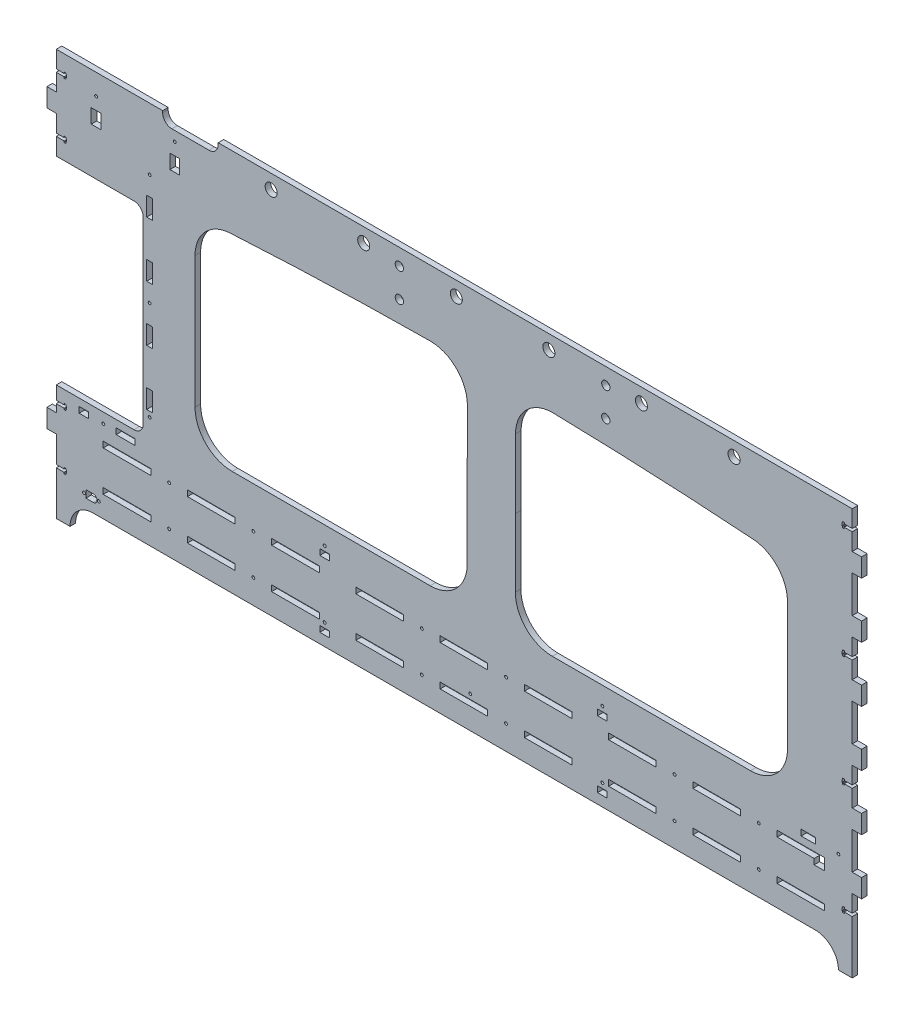
SolidWorks part; units mm, degrees
ref_plane "Płaszczyzna przednia" through (0, 0, 0) normal (0, 0, 1) x (1, 0, 0)
ref_plane "Płaszczyzna górna" through (0, 0, 0) normal (0, 1, 0) x (1, 0, 0)
ref_plane "Płaszczyzna prawa" through (0, 0, 0) normal (1, 0, 0) x (0, 0, -1)
sketch "Szkic1" plane through (0, 0, 0) normal (0, 0, 1) x (1, 0, 0)
  line L0 (0, -69.604) -> (0, -508.604)
  line L1 (0, -69.604) -> (880, -69.604)
  line L2 (0, -508.604) -> (880, -508.604)
  line L3 (880, -69.604) -> (880, -508.604)
  dimension "D1" = 880
  dimension "D2" = 439
extrude "Dodanie-wyciągnięcie1" add sketch "Szkic1" along normal blind 6
sketch "Szkic2" plane through (0, 0, 6) normal (0, 0, 1) x (1, 0, 0)
  line L0 (25, -508.604) -> (855, -508.604)
  line L1 (0, -508.604) -> (880, -508.604) construction
  line L4 (50, -483.604) -> (830, -483.604)
  arc A0 (855, -508.604) -> (830, -483.604) centre (830, -508.604) ccw
  arc A1 (25, -508.604) -> (50, -483.604) centre (50, -508.604) cw
extrude "Wytnij-wyciągnięcie1" cut sketch "Szkic2" against normal blind 6
sketch "Szkic3" plane through (0, 0, 6) normal (0, 0, 1) x (1, 0, 0)
  line L0 (160, -187.6437) -> (160, -329.604)
  line L1 (800, -191.4926) -> (800, -329.604)
  line L2 (200, -369.604) -> (760, -369.604)
  line L3 (0, -69.604) -> (0, -508.604) construction
  line L4 (880, -508.604) -> (880, -69.604) construction
  line L6 (830, -483.604) -> (50, -483.604) construction
  arc A2 (760, -369.604) -> (800, -329.604) centre (760, -329.604) ccw
  arc A3 (762.855, -151.5946) -> (197.6937, -147.7103) centre (450.2341, -4520.4043) ccw
  arc A4 (160, -329.604) -> (200, -369.604) centre (200, -329.604) ccw
  arc A5 (197.6937, -147.7103) -> (160, -187.6437) centre (200, -187.6437) ccw
  arc A6 (762.855, -151.5946) -> (800, -191.4926) centre (760, -191.4926) cw
  dimension "D1" = 40
  dimension "D5" = 40
  dimension "D2" = 160
  dimension "D3" = 114
  dimension "D4" = 80
extrude "Wytnij-wyciągnięcie2" cut sketch "Szkic3" against normal blind 6
sketch "Szkic4" plane through (0, 0, 6) normal (0, 0, 1) x (1, 0, 0)
  line L0 (0, -69.604) -> (0, -508.604) construction
  line L1 (94, -383.604) -> (0, -383.604)
  line L2 (0, -383.604) -> (0, -169.604)
  line L3 (104, -179.604) -> (104, -373.604)
  line L4 (0, -169.604) -> (94, -169.604)
  line L5 (880, -69.604) -> (0, -69.604) construction
  line L6 (830, -483.604) -> (50, -483.604) construction
  arc A0 (94, -383.604) -> (104, -373.604) centre (94, -373.604) ccw
  arc A1 (94, -169.604) -> (104, -179.604) centre (94, -179.604) cw
  dimension "D4" = 10
  dimension "D5" = 104
  dimension "D1" = 100
  dimension "D2" = 100
extrude "Wytnij-wyciągnięcie3" cut sketch "Szkic4" against normal blind 6
sketch "Szkic5" plane through (0, 0, 0) normal (0, 0, -1) x (-1, 0, 0)
  line L0 (-880, -69.604) -> (-880, -109.604)
  line L1 (-880, -69.604) -> (-869.9, -69.604)
  line L2 (-880, -109.604) -> (-869.9, -109.604)
  line L3 (-869.9, -69.604) -> (-869.9, -109.604)
  line L4 (-880, -508.604) -> (-880, -67.104) construction
  line L5 (-880, -69.604) -> (0, -69.604) construction
  dimension "D1" = 10.1
  dimension "D2" = 40
  dimension "D3" = 0
  dimension "D4" = 0
extrude "Wytnij-wyciągnięcie5" cut sketch "Szkic5" against normal blind 6
pattern_linear "Szyk liniowy1" count 8 spacing 60 along (0, -1, 0) count 2 spacing 400 along (0, -1, 0) of "Wytnij-wyciągnięcie5"
sketch "Szkic6" plane through (0, 0, 0) normal (0, 0, -1) x (-1, 0, 0)
  line L0 (-869.9, -88.054) -> (-869.9, -91.154)
  line L1 (-869.9, -88.054) -> (-861.4, -88.054)
  line L2 (-869.9, -91.154) -> (-861.4, -91.154)
  line L3 (-858.9, -88.054) -> (-858.9, -91.154)
  line L4 (-869.9, -109.604) -> (-869.9, -69.604) construction
  line L5 (-869.9, -69.604) -> (0, -69.604) construction
  line L6 (-861.4, -88.054) -> (-861.4, -86.684)
  line L7 (-859.4, -88.054) -> (-859.4, -86.684)
  line L8 (-861.4, -86.684) -> (-859.4, -86.684)
  line L9 (-859.4, -91.154) -> (-858.9, -91.154)
  line L10 (-859.4, -88.054) -> (-858.9, -88.054)
  line L11 (-861.4, -91.154) -> (-861.4, -92.534)
  line L12 (-859.4, -91.154) -> (-859.4, -92.534)
  line L13 (-861.4, -92.534) -> (-859.4, -92.534)
  point P6 (-869.9, -89.604)
  dimension "D1" = 3.1
  dimension "D2" = 2
  dimension "D3" = 2
  dimension "D4" = 5.85
  dimension "D5" = 1.38
  dimension "D6" = 0.5
  dimension "D7" = 11
  dimension "D8" = 0
  dimension "D9" = 20
extrude "Wytnij-wyciągnięcie6" cut sketch "Szkic6" against normal through all
pattern_linear "Szyk liniowy2" count 4 spacing 120 along (0, -1, 0) of "Wytnij-wyciągnięcie6"
ref_plane "Płaszczyzna1" through (440, 0, 0) normal (1, 0, 0) x (0, 0, -1)
mirror "Lustro1" about plane through (440, 0, 0) normal (1, 0, 0) of "Szyk liniowy1"
sketch "Szkic16" plane through (0, 0, 0) normal (0, 0, -1) x (-1, 0, 0)
  line L1 (-829, -417.104) -> (-840, -417.104) construction
  line L3 (-840, -423.104) -> (-829, -423.104) construction
  line L5 (-829, -417.104) -> (-840, -417.104) construction
  line L7 (-840, -423.104) -> (-829, -423.104) construction
  line L9 (-829, -417.104) -> (-840, -417.104) construction
  line L11 (-840, -423.104) -> (-829, -423.104) construction
  line L13 (-829, -417.104) -> (-840, -417.104) construction
  line L15 (-840, -423.104) -> (-829, -423.104) construction
  line L17 (-829, -417.104) -> (-840, -417.104) construction
  line L19 (-840, -423.104) -> (-829, -423.104) construction
  line L21 (-829, -417.104) -> (-840, -417.104) construction
  line L23 (-840, -423.104) -> (-829, -423.104) construction
  line L25 (-829, -417.104) -> (-840, -417.104) construction
  line L27 (-840, -423.104) -> (-829, -423.104) construction
  line L28 (-828.8, -423.304) -> (-828.8, -416.904)
  line L29 (-828.8, -416.904) -> (-840.2, -416.904)
  line L30 (-840.2, -416.904) -> (-840.2, -423.304)
  line L31 (-840.2, -423.304) -> (-828.8, -423.304)
  line L32 (-828.8, -423.304) -> (-828.8, -416.904)
  line L33 (-828.8, -416.904) -> (-840.2, -416.904)
  line L34 (-840.2, -416.904) -> (-840.2, -423.304)
  line L35 (-840.2, -423.304) -> (-828.8, -423.304)
  line L36 (-828.8, -423.304) -> (-828.8, -416.904)
  line L37 (-828.8, -416.904) -> (-840.2, -416.904)
  line L38 (-840.2, -416.904) -> (-840.2, -423.304)
  line L39 (-840.2, -423.304) -> (-828.8, -423.304)
  line L40 (-828.8, -423.304) -> (-828.8, -416.904)
  line L41 (-828.8, -416.904) -> (-840.2, -416.904)
  line L42 (-840.2, -416.904) -> (-840.2, -423.304)
  line L43 (-840.2, -423.304) -> (-828.8, -423.304)
  line L44 (-828.8, -423.304) -> (-828.8, -416.904)
  line L45 (-828.8, -416.904) -> (-840.2, -416.904)
  line L46 (-840.2, -416.904) -> (-840.2, -423.304)
  line L47 (-840.2, -423.304) -> (-828.8, -423.304)
  line L48 (-828.8, -423.304) -> (-828.8, -416.904)
  line L49 (-828.8, -416.904) -> (-840.2, -416.904)
  line L50 (-840.2, -416.904) -> (-840.2, -423.304)
  line L51 (-840.2, -423.304) -> (-828.8, -423.304)
  line L52 (-828.8, -423.304) -> (-828.8, -416.904)
  line L53 (-828.8, -416.904) -> (-840.2, -416.904)
  line L54 (-840.2, -416.904) -> (-840.2, -423.304)
  line L55 (-840.2, -423.304) -> (-828.8, -423.304)
  line L56 (-828.8, -423.304) -> (-828.8, -416.904)
  line L57 (-828.8, -416.904) -> (-840.2, -416.904)
  line L58 (-840.2, -416.904) -> (-840.2, -423.304)
  line L59 (-840.2, -423.304) -> (-828.8, -423.304)
  line L64 (-828.8, -423.304) -> (-828.8, -416.904)
  line L65 (-828.8, -416.904) -> (-840.2, -416.904)
  line L66 (-840.2, -416.904) -> (-840.2, -423.304)
  line L67 (-840.2, -423.304) -> (-828.8, -423.304)
  line L85 (-829, -417.104) -> (-840, -417.104) construction
  line L87 (-840, -423.104) -> (-829, -423.104) construction
  line L94 (-840, -417.104) -> (-840, -423.104) construction
  line L95 (-840, -423.104) -> (-829, -423.104) construction
  line L96 (-829, -423.104) -> (-829, -417.104)
  line L97 (-829, -417.104) -> (-840, -417.104)
  line L98 (-840, -417.104) -> (-840, -423.104)
  line L99 (-840, -423.104) -> (-829, -423.104)
  line L100 (-829, -423.104) -> (-829, -417.104)
  line L101 (-829, -417.104) -> (-840, -417.104)
  line L102 (-840, -417.104) -> (-840, -423.104)
  line L103 (-840, -423.104) -> (-829, -423.104)
  line L104 (-829, -423.104) -> (-829, -417.104)
  line L105 (-829, -417.104) -> (-840, -417.104)
  line L106 (-840, -417.104) -> (-840, -423.104)
  line L107 (-840, -423.104) -> (-829, -423.104)
  line L108 (-829, -423.104) -> (-829, -417.104)
  line L109 (-829, -417.104) -> (-840, -417.104)
  line L110 (-840, -417.104) -> (-840, -423.104)
  line L111 (-840, -423.104) -> (-829, -423.104)
  line L112 (-829, -423.104) -> (-829, -417.104)
  line L113 (-829, -417.104) -> (-840, -417.104)
  line L114 (-840, -417.104) -> (-840, -423.104)
  line L115 (-840, -423.104) -> (-829, -423.104)
  line L116 (-829, -423.104) -> (-829, -417.104)
  line L117 (-829, -417.104) -> (-840, -417.104)
  line L118 (-840, -417.104) -> (-840, -423.104)
  line L119 (-840, -423.104) -> (-829, -423.104)
  line L120 (-829, -423.104) -> (-829, -417.104)
  line L121 (-829, -417.104) -> (-840, -417.104)
  line L122 (-840, -417.104) -> (-840, -423.104)
  line L123 (-840, -423.104) -> (-829, -423.104)
  line L124 (-829, -423.104) -> (-829, -417.104)
  line L125 (-829, -417.104) -> (-840, -417.104)
  line L126 (-840, -417.104) -> (-840, -423.104)
  line L127 (-840, -423.104) -> (-829, -423.104)
  line L132 (-829, -423.104) -> (-829, -417.104)
  line L133 (-829, -417.104) -> (-840, -417.104)
  line L134 (-840, -417.104) -> (-840, -423.104)
  line L135 (-840, -423.104) -> (-829, -423.104)
  dimension "D1" = 0.2
sketch "Szkic18" plane through (0, 0, 0) normal (0, 0, -1) x (-1, 0, 0)
  line L32 (-840.2, -416.904) -> (-840.2, -423.304) construction
  line L33 (-840.2, -423.304) -> (-828.8, -423.304) construction
  line L34 (-828.8, -423.304) -> (-828.8, -416.904) construction
  line L35 (-828.8, -416.904) -> (-840.2, -416.904) construction
  line L72 (-840.2, -416.904) -> (-840.2, -423.304)
  line L73 (-840.2, -423.304) -> (-828.8, -423.304)
  line L74 (-828.8, -423.304) -> (-828.8, -416.904)
  line L75 (-828.8, -416.904) -> (-840.2, -416.904)
extrude "Wytnij-wyciągnięcie9" cut sketch "Szkic18" against normal blind 6
sketch "Szkic19" plane through (0, 0, 0) normal (0, 0, -1) x (-1, 0, 0)
  line L4 (-830, -483.604) -> (-50, -483.604) construction
  circle A1 centre (-769, -414.104) radius 1.55
  dimension "D1" = 69.5
extrude "Wytnij-wyciągnięcie10" cut sketch "Szkic19" against normal blind 6
sketch "Szkic21" plane through (0, 0, 0) normal (0, 0, -1) x (-1, 0, 0)
  line L0 (-305, -459.4227) -> (-295, -459.4227) construction
  line L1 (-305, -462.5227) -> (-295, -462.5227) construction
  line L2 (-305, -459.4227) -> (-295, -459.4227)
  line L3 (-305, -462.5227) -> (-295, -462.5227)
  line L4 (-295, -472.5227) -> (-295, -466.5227)
  line L5 (-295, -466.5227) -> (-305, -466.5227)
  line L6 (-305, -466.5227) -> (-305, -472.5227)
  line L7 (-305, -472.5227) -> (-295, -472.5227)
  line L8 (-295, -472.5227) -> (-295, -466.5227)
  line L9 (-295, -466.5227) -> (-305, -466.5227)
  line L10 (-305, -466.5227) -> (-305, -472.5227)
  line L11 (-305, -472.5227) -> (-295, -472.5227)
  line L12 (-300, -459.4227) -> (-300.0697, -462.5227)
  line L13 (-305.2, -466.3227) -> (-305.2, -472.7227)
  line L14 (-305.2, -472.7227) -> (-294.8, -472.7227)
  line L15 (-294.8, -472.7227) -> (-294.8, -466.3227)
  line L16 (-294.8, -466.3227) -> (-305.2, -466.3227)
  circle A0 centre (-300.0348, -460.9727) radius 1.55
  dimension "D2" = 3.1
  dimension "D1" = 0
  dimension "D3" = 0.2
sketch "Szkic22" plane through (0, 0, 0) normal (0, 0, -1) x (-1, 0, 0)
  line L0 (-305.2, -466.3227) -> (-305.2, -472.7227) construction
  line L1 (-305.2, -472.7227) -> (-294.8, -472.7227) construction
  line L2 (-294.8, -472.7227) -> (-294.8, -466.3227) construction
  line L3 (-294.8, -466.3227) -> (-305.2, -466.3227) construction
  line L4 (-305.2, -466.3227) -> (-305.2, -472.7227)
  line L5 (-305.2, -472.7227) -> (-294.8, -472.7227)
  line L6 (-294.8, -472.7227) -> (-294.8, -466.3227)
  line L7 (-294.8, -466.3227) -> (-305.2, -466.3227)
  circle A0 centre (-300.0348, -460.9727) radius 1.55 construction
  circle A1 centre (-300.0348, -460.9727) radius 1.55
extrude "Wytnij-wyciągnięcie11" cut sketch "Szkic22" against normal blind 6
pattern_linear "Szyk liniowy5" count 2 spacing 300 along (1, 0, 0) of "Wytnij-wyciągnięcie11"
sketch "Szkic25" plane through (0, 0, 0) normal (0, 0, -1) x (-1, 0, 0)
  line L0 (-853.45, -403.104) -> (-853.45, -397.104) construction
  line L1 (-856.55, -403.104) -> (-856.55, -397.104) construction
  line L2 (-853.45, -403.104) -> (-853.45, -397.104)
  line L3 (-856.55, -403.104) -> (-856.55, -397.104)
  line L4 (-830.2, -396.904) -> (-830.2, -403.304)
  line L5 (-830.2, -403.304) -> (-814.8, -403.304)
  line L6 (-814.8, -403.304) -> (-814.8, -396.904)
  line L7 (-814.8, -396.904) -> (-830.2, -396.904)
  line L8 (-830, -397.104) -> (-830, -403.104)
  line L9 (-830, -403.104) -> (-815, -403.104)
  line L10 (-815, -403.104) -> (-815, -397.104)
  line L11 (-815, -397.104) -> (-830, -397.104)
  line L12 (-830, -397.104) -> (-830, -403.104)
  line L13 (-830, -403.104) -> (-815, -403.104)
  line L14 (-815, -403.104) -> (-815, -397.104)
  line L15 (-815, -397.104) -> (-830, -397.104)
  line L16 (-856.55, -400.104) -> (-853.45, -400.104)
  circle A0 centre (-855, -400.104) radius 1.55
  dimension "D3" = 3.1
  dimension "D1" = 0
  dimension "D2" = 0.2
sketch "Szkic26" plane through (0, 0, 0) normal (0, 0, -1) x (-1, 0, 0)
  line L0 (-830.2, -396.904) -> (-830.2, -403.304) construction
  line L1 (-830.2, -403.304) -> (-814.8, -403.304) construction
  line L2 (-814.8, -403.304) -> (-814.8, -396.904) construction
  line L3 (-814.8, -396.904) -> (-830.2, -396.904) construction
  line L4 (-830.2, -396.904) -> (-830.2, -403.304)
  line L5 (-830.2, -403.304) -> (-814.8, -403.304)
  line L6 (-814.8, -403.304) -> (-814.8, -396.904)
  line L7 (-814.8, -396.904) -> (-830.2, -396.904)
  circle A0 centre (-855, -400.104) radius 1.55 construction
  circle A1 centre (-855, -400.104) radius 1.55
extrude "Wytnij-wyciągnięcie12" cut sketch "Szkic26" against normal blind 6
sketch "Szkic27" plane through (0, 0, 0) normal (0, 0, -1) x (-1, 0, 0)
  line L0 (-605, -387.5049) -> (-595, -387.5049) construction
  line L1 (-605, -390.6049) -> (-595, -390.6049) construction
  line L2 (-305, -387.5049) -> (-295, -387.5049) construction
  line L3 (-305, -390.6049) -> (-295, -390.6049) construction
  line L4 (-605, -387.5049) -> (-595, -387.5049)
  line L5 (-605, -390.6049) -> (-595, -390.6049)
  line L6 (-305, -387.5049) -> (-295, -387.5049)
  line L7 (-305, -390.6049) -> (-295, -390.6049)
  line L16 (-295, -400.6049) -> (-295, -394.6049)
  line L17 (-295, -394.6049) -> (-305, -394.6049)
  line L18 (-305, -394.6049) -> (-305, -400.6049)
  line L19 (-305, -400.6049) -> (-295, -400.6049)
  line L20 (-605, -400.6049) -> (-605, -394.6049) construction
  line L21 (-605, -394.6049) -> (-595, -394.6049) construction
  line L22 (-595, -400.6049) -> (-595, -394.6049) construction
  line L23 (-605, -400.6049) -> (-595, -400.6049) construction
  line L24 (-605, -400.6049) -> (-605, -394.6049)
  line L25 (-605, -394.6049) -> (-595, -394.6049)
  line L26 (-595, -400.6049) -> (-595, -394.6049)
  line L27 (-605, -400.6049) -> (-595, -400.6049)
  line L32 (-300, -387.5049) -> (-300, -390.6049)
  line L33 (-600, -387.5049) -> (-600, -390.6049)
  line L34 (-605.2, -400.8049) -> (-605.2, -394.4049)
  line L35 (-605.2, -394.4049) -> (-594.8, -394.4049)
  line L36 (-594.8, -400.8049) -> (-594.8, -394.4049)
  line L37 (-605.2, -400.8049) -> (-594.8, -400.8049)
  line L38 (-295, -400.6049) -> (-295, -394.6049)
  line L39 (-295, -394.6049) -> (-305, -394.6049)
  line L40 (-305, -394.6049) -> (-305, -400.6049)
  line L41 (-305, -400.6049) -> (-295, -400.6049)
  line L47 (-294.8, -400.8049) -> (-294.8, -394.4049)
  line L48 (-294.8, -394.4049) -> (-305.2, -394.4049)
  line L49 (-305.2, -394.4049) -> (-305.2, -400.8049)
  line L50 (-305.2, -400.8049) -> (-294.8, -400.8049)
  line L51 (-294.8, -400.8049) -> (-294.8, -394.4049)
  line L52 (-294.8, -394.4049) -> (-305.2, -394.4049)
  line L53 (-305.2, -394.4049) -> (-305.2, -400.8049)
  line L54 (-305.2, -400.8049) -> (-294.8, -400.8049)
  circle A0 centre (-600, -389.0549) radius 1.55
  circle A2 centre (-300, -389.0549) radius 1.55
  dimension "D5" = 3.1
  dimension "D1" = 0
  dimension "D2" = 0.2
  dimension "D3" = 0.2
sketch "Szkic28" plane through (0, 0, 0) normal (0, 0, -1) x (-1, 0, 0)
  line L8 (-605.2, -394.4049) -> (-594.8, -394.4049) construction
  line L9 (-605.2, -400.8049) -> (-605.2, -394.4049) construction
  line L10 (-605.2, -400.8049) -> (-594.8, -400.8049) construction
  line L11 (-594.8, -400.8049) -> (-594.8, -394.4049) construction
  line L12 (-305.2, -394.4049) -> (-305.2, -400.8049) construction
  line L13 (-294.8, -394.4049) -> (-305.2, -394.4049) construction
  line L14 (-294.8, -400.8049) -> (-294.8, -394.4049) construction
  line L15 (-305.2, -400.8049) -> (-294.8, -400.8049) construction
  line L16 (-605.2, -394.4049) -> (-594.8, -394.4049)
  line L17 (-605.2, -400.8049) -> (-605.2, -394.4049)
  line L18 (-605.2, -400.8049) -> (-594.8, -400.8049)
  line L19 (-594.8, -400.8049) -> (-594.8, -394.4049)
  line L20 (-305.2, -394.4049) -> (-305.2, -400.8049)
  line L21 (-294.8, -394.4049) -> (-305.2, -394.4049)
  line L22 (-294.8, -400.8049) -> (-294.8, -394.4049)
  line L23 (-305.2, -400.8049) -> (-294.8, -400.8049)
  circle A0 centre (-600, -389.0549) radius 1.55 construction
  circle A2 centre (-600, -389.0549) radius 1.55
  circle A3 centre (-300, -389.0549) radius 1.55 construction
  circle A4 centre (-300, -389.0549) radius 1.55
extrude "Wytnij-wyciągnięcie13" cut sketch "Szkic28" against normal blind 6
sketch "Szkic29" plane through (0, 0, 0) normal (0, 0, -1) x (-1, 0, 0)
  line L0 (-45, -391.604) -> (-35, -391.604) construction
  line L1 (-35, -397.604) -> (-35, -391.604) construction
  line L2 (-45, -397.604) -> (-45, -391.604) construction
  line L3 (-45, -397.604) -> (-35, -397.604) construction
  line L4 (-75, -397.604) -> (-75, -391.604) construction
  line L5 (-95, -397.604) -> (-95, -391.604) construction
  line L6 (-95, -391.604) -> (-75, -391.604) construction
  line L7 (-95, -397.604) -> (-75, -397.604) construction
  line L8 (-62.5, -397.604) -> (-62.5, -391.604) construction
  line L9 (-59.4, -397.604) -> (-59.4, -391.604) construction
  line L12 (-45, -391.604) -> (-35, -391.604)
  line L13 (-35, -397.604) -> (-35, -391.604)
  line L14 (-45, -397.604) -> (-45, -391.604)
  line L15 (-45, -397.604) -> (-35, -397.604)
  line L16 (-75, -397.604) -> (-75, -391.604)
  line L17 (-95, -397.604) -> (-95, -391.604)
  line L18 (-95, -391.604) -> (-75, -391.604)
  line L19 (-95, -397.604) -> (-75, -397.604)
  line L20 (-62.5, -397.604) -> (-62.5, -391.604)
  line L21 (-59.4, -397.604) -> (-59.4, -391.604)
  line L24 (-62.5, -394.604) -> (-59.4, -394.604)
  line L27 (-95.2, -397.804) -> (-74.8, -397.804)
  line L28 (-74.8, -397.804) -> (-74.8, -391.404)
  line L29 (-95.2, -391.404) -> (-74.8, -391.404)
  line L30 (-95.2, -397.804) -> (-95.2, -391.404)
  line L31 (-45.2, -397.804) -> (-34.8, -397.804)
  line L32 (-34.8, -397.804) -> (-34.8, -391.404)
  line L33 (-45.2, -391.404) -> (-34.8, -391.404)
  line L34 (-45.2, -397.804) -> (-45.2, -391.404)
  circle A1 centre (-60.95, -394.604) radius 1.55
  dimension "D2" = 3.1
  dimension "D3" = 0.2
sketch "Szkic30" plane through (0, 0, 0) normal (0, 0, -1) x (-1, 0, 0)
  line L0 (-95.2, -391.404) -> (-74.8, -391.404) construction
  line L1 (-74.8, -397.804) -> (-74.8, -391.404) construction
  line L2 (-95.2, -397.804) -> (-74.8, -397.804) construction
  line L3 (-95.2, -397.804) -> (-95.2, -391.404) construction
  line L4 (-45.2, -397.804) -> (-45.2, -391.404) construction
  line L5 (-45.2, -391.404) -> (-34.8, -391.404) construction
  line L6 (-34.8, -397.804) -> (-34.8, -391.404) construction
  line L7 (-45.2, -397.804) -> (-34.8, -397.804) construction
  line L8 (-95.2, -391.404) -> (-74.8, -391.404)
  line L9 (-74.8, -397.804) -> (-74.8, -391.404)
  line L10 (-95.2, -397.804) -> (-74.8, -397.804)
  line L11 (-95.2, -397.804) -> (-95.2, -391.404)
  line L12 (-45.2, -397.804) -> (-45.2, -391.404)
  line L13 (-45.2, -391.404) -> (-34.8, -391.404)
  line L14 (-34.8, -397.804) -> (-34.8, -391.404)
  line L15 (-45.2, -397.804) -> (-34.8, -397.804)
  circle A1 centre (-60.95, -394.604) radius 1.55 construction
  circle A3 centre (-60.95, -394.604) radius 1.55
extrude "Wytnij-wyciągnięcie14" cut sketch "Szkic30" against normal blind 6
sketch "Szkic31" plane through (0, 0, 0) normal (0, 0, -1) x (-1, 0, 0)
  line L0 (-185, -69.604) -> (-125, -69.604)
  line L1 (-185, -69.604) -> (-185, -71.604)
  line L2 (-125, -69.604) -> (-125, -71.604)
  line L3 (-175, -81.604) -> (-135, -81.604)
  line L4 (-869.9, -69.604) -> (-10.1, -69.604) construction
  arc A0 (-125, -71.604) -> (-135, -81.604) centre (-135, -71.604) cw
  arc A1 (-185, -71.604) -> (-175, -81.604) centre (-175, -71.604) ccw
  dimension "D1" = 10
  dimension "D2" = 60
  dimension "D3" = 12
extrude "Wytnij-wyciągnięcie15" cut sketch "Szkic31" against normal blind 6
sketch "Szkic32" plane through (0, 0, 0) normal (0, 0, -1) x (-1, 0, 0)
  line L0 (-114, -365.154) -> (-108, -365.154) construction
  line L1 (-114, -362.054) -> (-108, -362.054) construction
  line L2 (-114, -365.154) -> (-108, -365.154)
  line L3 (-114, -362.054) -> (-108, -362.054)
  line L4 (-111, -365.154) -> (-111, -362.054)
  circle A0 centre (-111, -363.604) radius 1.55
  dimension "D1" = 3.1
sketch "Szkic33" plane through (0, 0, 0) normal (0, 0, -1) x (-1, 0, 0)
  circle A0 centre (-111, -363.604) radius 1.55 construction
  circle A1 centre (-111, -363.604) radius 1.55
extrude "Wytnij-wyciągnięcie16" cut sketch "Szkic33" against normal blind 6
pattern_linear "Szyk liniowy6" count 2 spacing 107 along (0, 1, 0) count 2 spacing 227 along (0, 1, 0) of "Wytnij-wyciągnięcie16"
sketch "Szkic34" plane through (0, 0, 0) normal (0, 0, -1) x (-1, 0, 0)
  line L0 (-107.8, -357.804) -> (-107.8, -337.404)
  line L1 (-107.8, -337.404) -> (-114.2, -337.404)
  line L2 (-114.2, -337.404) -> (-114.2, -357.804)
  line L3 (-114.2, -357.804) -> (-107.8, -357.804)
  line L4 (-108, -357.604) -> (-108, -337.604)
  line L5 (-108, -337.604) -> (-114, -337.604)
  line L6 (-114, -337.604) -> (-114, -357.604)
  line L7 (-114, -357.604) -> (-108, -357.604)
  line L8 (-108, -357.604) -> (-108, -337.604)
  line L9 (-108, -337.604) -> (-114, -337.604)
  line L10 (-114, -337.604) -> (-114, -357.604)
  line L11 (-114, -357.604) -> (-108, -357.604)
  dimension "D1" = 0
  dimension "D2" = 0.2
sketch "Szkic35" plane through (0, 0, 0) normal (0, 0, -1) x (-1, 0, 0)
  line L0 (-107.8, -357.804) -> (-107.8, -337.404) construction
  line L1 (-107.8, -337.404) -> (-114.2, -337.404) construction
  line L2 (-114.2, -337.404) -> (-114.2, -357.804) construction
  line L3 (-114.2, -357.804) -> (-107.8, -357.804) construction
  line L4 (-107.8, -357.804) -> (-107.8, -337.404)
  line L5 (-107.8, -337.404) -> (-114.2, -337.404)
  line L6 (-114.2, -337.404) -> (-114.2, -357.804)
  line L7 (-114.2, -357.804) -> (-107.8, -357.804)
extrude "Wytnij-wyciągnięcie17" cut sketch "Szkic35" against normal blind 6
pattern_linear "Szyk liniowy7" count 4 spacing 60 along (0, 1, 0) of "Wytnij-wyciągnięcie17"
sketch "Szkic37" plane through (0, 0, 0) normal (0, 0, -1) x (-1, 0, 0)
  line L0 (-50.1, -473.604) -> (-42.1, -473.604)
  line L1 (-830, -483.604) -> (-50, -483.604) construction
  line L2 (-42.1, -473.604) -> (-42.1, -465.604)
  line L3 (-50.1, -465.604) -> (-42.1, -465.604)
  line L4 (-10.1, -508.604) -> (-10.1, -429.604) construction
  circle A0 centre (-56.1, -469.604) radius 1.55
  circle A1 centre (-40.1, -469.604) radius 1.55
  arc A2 (-50.1, -465.604) -> (-50.1, -473.604) centre (-50.1, -469.604) ccw
  dimension "D3" = 3.1
  dimension "D4" = 3.1
  dimension "D5" = 16
  dimension "D6" = 2
  dimension "D7" = 4
  dimension "D8" = 4
  dimension "D9" = 4
  dimension "D10" = 8
  dimension "D11" = 8
  dimension "D2" = 30
  dimension "D1" = 8
  dimension "D12" = 10
extrude "Wytnij-wyciągnięcie18" cut sketch "Szkic37" against normal blind 6
sketch "Szkic39" plane through (0, 0, 0) normal (0, 0, -1) x (-1, 0, 0)
  line L0 (-10.1, -88.054) -> (-10.1, -91.154)
  line L1 (-10.1, -88.054) -> (-18.6, -88.054)
  line L2 (-10.1, -91.154) -> (-18.6, -91.154)
  line L3 (-21.1, -88.054) -> (-21.1, -91.154)
  line L4 (-10.1, -109.604) -> (-10.1, -69.604) construction
  line L5 (-20.6, -86.679) -> (-20.6, -88.054)
  line L6 (-20.6, -86.679) -> (-18.6, -86.679)
  line L7 (-20.6, -92.529) -> (-18.6, -92.529)
  line L8 (-18.6, -86.679) -> (-18.6, -88.054)
  line L9 (-20.6, -91.154) -> (-20.6, -92.529)
  line L10 (-20.6, -88.054) -> (-21.1, -88.054)
  line L11 (-18.6, -91.154) -> (-18.6, -92.529)
  line L12 (-20.6, -91.154) -> (-21.1, -91.154)
  line L13 (-125, -69.604) -> (-10.1, -69.604) construction
  point P14 (-10.1, -89.604)
  dimension "D1" = 11
  dimension "D2" = 3.1
  dimension "D3" = 5.85
  dimension "D4" = 1.375
  dimension "D5" = 0.5
  dimension "D6" = 2
  dimension "D7" = 20
extrude "Wytnij-wyciągnięcie20" cut sketch "Szkic39" against normal blind 10
pattern_linear "Szyk liniowy9" count 2 spacing 60 along (0, -1, 0) count 2 spacing 310 along (0, -1, 0) of "Wytnij-wyciągnięcie20"
sketch "Szkic41" plane through (0, 0, 0) normal (0, 0, -1) x (-1, 0, 0)
  line L0 (-224.5469, -454.4216) -> (-224.5469, -460.4216) construction
  line L1 (-221.4469, -454.4216) -> (-221.4469, -460.4216) construction
  line L2 (-224.5469, -454.4216) -> (-224.5469, -460.4216)
  line L3 (-221.4469, -454.4216) -> (-221.4469, -460.4216)
  line L4 (-224.5469, -457.4216) -> (-221.4469, -457.4216)
  circle A0 centre (-222.9969, -457.4216) radius 1.55
  dimension "D1" = 3.1
sketch "Szkic43" plane through (0, 0, 0) normal (0, 0, -1) x (-1, 0, 0)
  circle A1 centre (-742.237, -84.9147) radius 3.2
  circle A3 centre (-742.237, -84.9147) radius 6.5
  dimension "D1" = 13
sketch "Szkic44" plane through (0, 0, 0) normal (0, 0, -1) x (-1, 0, 0)
  circle A1 centre (-742.237, -84.9147) radius 6.5 construction
  circle A2 centre (-742.237, -84.9147) radius 6.5
extrude "Wytnij-wyciągnięcie22" cut sketch "Szkic44" against normal blind 10
pattern_linear "Szyk liniowy10" count 6 spacing 100 along (-1, 0, 0) of "Wytnij-wyciągnięcie22"
sketch "Szkic45" plane through (0, 0, 0) normal (0, 0, -1) x (-1, 0, 0)
  line L0 (-125, -69.604) -> (-10.1, -69.604) construction
  line L8 (-143.3, -120.804) -> (-132.9, -120.804)
  line L9 (-143.3, -105.404) -> (-143.3, -120.804)
  line L10 (-132.9, -105.404) -> (-143.3, -105.404)
  line L11 (-132.9, -120.804) -> (-132.9, -105.404)
  line L12 (-58.3, -105.404) -> (-58.3, -120.804)
  line L13 (-47.9, -105.404) -> (-58.3, -105.404)
  line L14 (-58.3, -120.804) -> (-47.9, -120.804)
  line L15 (-47.9, -120.804) -> (-47.9, -105.404)
  circle A2 centre (-138.1, -92.154) radius 1.55
  circle A3 centre (-53.1, -92.154) radius 1.55
  dimension "D9" = 85
  dimension "D1" = 15.4
  dimension "D2" = 15.4
  dimension "D3" = 13.25
  dimension "D4" = 13.25
  dimension "D5" = 13.25
  dimension "D6" = 22.55
  dimension "D7" = 85
  dimension "D8" = 10.4
extrude "Wytnij-wyciągnięcie23" cut sketch "Szkic45" against normal blind 10
sketch "Szkic47" plane through (0, 0, 0) normal (0, 0, -1) x (-1, 0, 0)
  line L0 (-770.55, -460.5227) -> (-770.55, -454.5227) construction
  line L1 (-767.45, -460.5227) -> (-767.45, -454.5227) construction
  line L2 (-679.55, -460.5227) -> (-679.55, -454.5227) construction
  line L3 (-676.45, -460.5227) -> (-676.45, -454.5227) construction
  line L4 (-497.55, -460.5227) -> (-497.55, -454.5227) construction
  line L5 (-494.45, -460.5227) -> (-494.45, -454.5227) construction
  line L6 (-406.55, -460.5227) -> (-406.55, -454.5227) construction
  line L7 (-403.45, -460.5227) -> (-403.45, -454.5227) construction
  line L8 (-224.5469, -454.4216) -> (-224.5469, -460.4216) construction
  line L9 (-221.4469, -454.4216) -> (-221.4469, -460.4216) construction
  line L10 (-133.5469, -454.4216) -> (-133.5469, -460.4216) construction
  line L11 (-130.4469, -454.4216) -> (-130.4469, -460.4216) construction
  line L12 (-770.55, -460.5227) -> (-770.55, -454.5227)
  line L13 (-767.45, -460.5227) -> (-767.45, -454.5227)
  line L14 (-679.55, -460.5227) -> (-679.55, -454.5227)
  line L15 (-676.45, -460.5227) -> (-676.45, -454.5227)
  line L16 (-497.55, -460.5227) -> (-497.55, -454.5227)
  line L17 (-494.45, -460.5227) -> (-494.45, -454.5227)
  line L18 (-406.55, -460.5227) -> (-406.55, -454.5227)
  line L19 (-403.45, -460.5227) -> (-403.45, -454.5227)
  line L20 (-224.5469, -454.4216) -> (-224.5469, -460.4216)
  line L21 (-221.4469, -454.4216) -> (-221.4469, -460.4216)
  line L22 (-133.5469, -454.4216) -> (-133.5469, -460.4216)
  line L23 (-130.4469, -454.4216) -> (-130.4469, -460.4216)
  line L24 (-130.4469, -457.4216) -> (-133.5469, -457.4216)
  line L25 (-221.4469, -457.4216) -> (-224.5469, -457.4216)
  line L26 (-403.45, -457.5227) -> (-406.55, -457.5227)
  line L27 (-494.45, -457.5227) -> (-497.55, -457.5227)
  line L28 (-676.45, -457.5227) -> (-679.55, -457.5227)
  line L29 (-767.45, -457.5227) -> (-770.55, -457.5227)
  circle A0 centre (-769, -457.5227) radius 1.55
  circle A1 centre (-678, -457.5227) radius 1.55
  circle A2 centre (-496, -457.5227) radius 1.55
  circle A3 centre (-405, -457.5227) radius 1.55
  circle A4 centre (-222.9969, -457.4216) radius 1.55
  circle A5 centre (-131.9969, -457.4216) radius 1.55
  dimension "D1" = 3.1
  dimension "D2" = 3.1
  dimension "D3" = 3.1
  dimension "D4" = 3.1
  dimension "D5" = 3.1
  dimension "D6" = 3.1
sketch "Szkic49" plane through (0, 0, 0) normal (0, 0, -1) x (-1, 0, 0)
  circle A0 centre (-222.9969, -457.4216) radius 1.55 construction
  circle A1 centre (-131.9969, -457.4216) radius 1.55 construction
  circle A2 centre (-405, -457.5227) radius 1.55 construction
  circle A3 centre (-496, -457.5227) radius 1.55 construction
  circle A4 centre (-678, -457.5227) radius 1.55 construction
  circle A5 centre (-769, -457.5227) radius 1.55 construction
  circle A6 centre (-222.9969, -457.4216) radius 1.55
  circle A7 centre (-131.9969, -457.4216) radius 1.55
  circle A8 centre (-405, -457.5227) radius 1.55
  circle A9 centre (-496, -457.5227) radius 1.55
  circle A10 centre (-678, -457.5227) radius 1.55
  circle A11 centre (-769, -457.5227) radius 1.55
extrude "Wytnij-wyciągnięcie26" cut sketch "Szkic49" against normal blind 10
pattern_linear "Szyk liniowy12" count 2 spacing 91 along (-1, 0, 0) count 3 spacing 273 along (-1, 0, 0) of "Wytnij-wyciągnięcie10"
sketch "Szkic51" plane through (0, 0, 0) normal (0, 0, -1) x (-1, 0, 0)
  line L0 (-789, -417.104) -> (-789, -411.104) construction
  line L1 (-789, -411.104) -> (-840, -411.104) construction
  line L2 (-840, -411.104) -> (-840, -417.104) construction
  line L3 (-840, -417.104) -> (-789, -417.104) construction
  line L20 (-789, -417.104) -> (-789, -411.104)
  line L21 (-789, -411.104) -> (-840, -411.104)
  line L22 (-840, -411.104) -> (-840, -417.104)
  line L23 (-840, -417.104) -> (-789, -417.104)
  line L56 (-788.8, -410.904) -> (-840.2, -410.904)
  line L57 (-840.2, -410.904) -> (-840.2, -417.304)
  line L58 (-840.2, -417.304) -> (-788.8, -417.304)
  line L59 (-788.8, -417.304) -> (-788.8, -410.904)
  dimension "D5" = 0.2
sketch "Szkic52" plane through (0, 0, 0) normal (0, 0, -1) x (-1, 0, 0)
  line L0 (-788.8, -410.904) -> (-840.2, -410.904) construction
  line L1 (-840.2, -410.904) -> (-840.2, -417.304) construction
  line L2 (-840.2, -417.304) -> (-788.8, -417.304) construction
  line L3 (-788.8, -417.304) -> (-788.8, -410.904) construction
  line L20 (-788.8, -410.904) -> (-840.2, -410.904)
  line L21 (-840.2, -410.904) -> (-840.2, -417.304)
  line L22 (-840.2, -417.304) -> (-788.8, -417.304)
  line L23 (-788.8, -417.304) -> (-788.8, -410.904)
extrude "Wytnij-wyciągnięcie27" cut sketch "Szkic52" against normal blind 6
pattern_linear "Szyk liniowy13" count 9 spacing 91 along (-1, 0, 0) of "Wytnij-wyciągnięcie27"
pattern_linear "Szyk liniowy4" count 2 spacing 43.42 along (0, -1, 0) of "Szyk liniowy13"
sketch "Szkic54" plane through (0, 0, 0) normal (0, 0, -1) x (-1, 0, 0)
  circle A0 centre (-603.737, -87.304) radius 1.55 construction
  circle A1 centre (-603.737, -118.304) radius 1.55 construction
  circle A2 centre (-380.737, -118.304) radius 1.55 construction
  circle A3 centre (-380.737, -87.304) radius 1.55 construction
  circle A4 centre (-603.737, -87.304) radius 1.55
  circle A5 centre (-603.737, -118.304) radius 1.55
  circle A6 centre (-380.737, -118.304) radius 1.55
  circle A7 centre (-380.737, -87.304) radius 1.55
  circle A8 centre (-380.737, -87.304) radius 4.5
  circle A9 centre (-380.737, -118.304) radius 4.5
  circle A10 centre (-603.737, -118.304) radius 4.5
  circle A11 centre (-603.737, -87.304) radius 4.5
  dimension "D1" = 9
  dimension "D2" = 9
  dimension "D3" = 9
  dimension "D4" = 9
sketch "Szkic55" plane through (0, 0, 0) normal (0, 0, -1) x (-1, 0, 0)
  circle A0 centre (-380.737, -87.304) radius 4.5 construction
  circle A1 centre (-380.737, -118.304) radius 4.5 construction
  circle A2 centre (-603.737, -118.304) radius 4.5 construction
  circle A3 centre (-603.737, -87.304) radius 4.5 construction
  circle A4 centre (-380.737, -87.304) radius 4.5
  circle A5 centre (-380.737, -118.304) radius 4.5
  circle A6 centre (-603.737, -118.304) radius 4.5
  circle A7 centre (-603.737, -87.304) radius 4.5
extrude "Wytnij-wyciągnięcie28" cut sketch "Szkic55" against normal blind 10
sketch "Szkic57" plane through (0, 0, 0) normal (0, 0, -1) x (-1, 0, 0)
  line L4 (-454, -255.9575) -> (-454, -329.604)
  line L5 (-454.2104, -180.685) -> (-454, -255.9575)
  line L6 (-506, -256.1602) -> (-506.209, -181.3733)
  line L7 (-506, -329.604) -> (-506, -256.1602)
  line L8 (-546, -369.604) -> (-414, -369.604)
  line L10 (-545.8769, -141.4864) -> (-546.2089, -137.5578)
  line L11 (-546.2089, -137.5578) -> (-415.0951, -137.5578)
  line L12 (-415.0951, -137.5578) -> (-415.0951, -140.583)
  arc A6 (-546, -369.604) -> (-506, -329.604) centre (-546, -329.604) ccw
  arc A7 (-454, -329.604) -> (-414, -369.604) centre (-414, -329.604) ccw
  arc A9 (-506.209, -181.3733) -> (-545.8769, -141.4864) centre (-546.2089, -181.4851) ccw
  arc A10 (-454.2104, -180.685) -> (-415.0951, -140.583) centre (-414.2105, -180.5732) cw
  point P17 (-506.3225, -140.7829)
  dimension "D1" = 40
extrude "Dodanie-wyciągnięcie2" add sketch "Szkic57" against normal blind 6 separate body
combine bodies "Połącz1" operation type add bodies to combine 149 151
sketch "Szkic58" plane through (0, 0, 0) normal (0, 0, -1) x (-1, 0, 0)
  line L0 (-424.8, -454.324) -> (-476.2, -454.324) construction
  circle A0 centre (-457.25, -449.024) radius 1.55
  point P4 (-392.5, -460.5227)
  dimension "D1" = 3.1
  dimension "D2" = 5.3
extrude "Wytnij-wyciągnięcie30" cut sketch "Szkic58" against normal blind 6
equation "\"tolerancja_wpusy\"=0.2"
equation "\"dlugosc_wpustu_duzy\"=20"
equation "\"srednica_otworu_M3\"=3.1"
equation "\"szerokosc_nogi_T\"=3.1"
equation "\"dlugosc_T_30\"=11"
equation "\"grubosc_na_nakretke_kwadrat\"=2"
equation "\"szerokosc_na_nakretke_kwadrat\"=5.85"
equation "\"wyokosc_nadstawki_T\"=0.5"
equation "\"D1@Szkic6\"=\"szerokosc_nogi_T\""
equation "\"D2@Szkic6\"=\"grubosc_na_nakretke_kwadrat\""
equation "\"D3@Szkic6\"=\"grubosc_na_nakretke_kwadrat\""
equation "\"D4@Szkic6\"=\"szerokosc_na_nakretke_kwadrat\""
equation "\"D6@Szkic6\"=\"wyokosc_nadstawki_T\""
equation "\"D7@Szkic6\"=\"dlugosc_T_30\""
equation "\"D3@Szkic25\" = \"srednica_otworu_M3\""
equation "\"D5@Szkic27\" = \"srednica_otworu_M3\""
equation "\"D2@Szkic29\" = \"srednica_otworu_M3\""
equation "\"D1@Szkic32\"=\"srednica_otworu_M3\""
equation "\"D3@Szkic37\"=\"srednica_otworu_M3\""
equation "\"D4@Szkic37\"=\"srednica_otworu_M3\""
equation "\"D2@Szkic39\"=\"szerokosc_nogi_T\""
equation "\"D3@Szkic39\"=\"szerokosc_na_nakretke_kwadrat\""
equation "\"D4@Szkic39\"=(\"szerokosc_na_nakretke_kwadrat\"-\"szerokosc_nogi_T\")/2"
equation "\"D5@Szkic39\"=\"wyokosc_nadstawki_T\""
equation "\"D6@Szkic39\"=\"grubosc_na_nakretke_kwadrat\""
equation "\"D1@Szkic41\"=\"srednica_otworu_M3\""
equation "\"D1@Szkic47\"=\"srednica_otworu_M3\""
equation "\"D2@Szkic47\"=\"srednica_otworu_M3\""
equation "\"D3@Szkic47\"=\"srednica_otworu_M3\""
equation "\"D4@Szkic47\"=\"srednica_otworu_M3\""
equation "\"D5@Szkic47\"=\"srednica_otworu_M3\""
equation "\"D6@Szkic47\"=\"srednica_otworu_M3\""
equation "\"D1@Szkic58\"=\"srednica_otworu_M3\""
